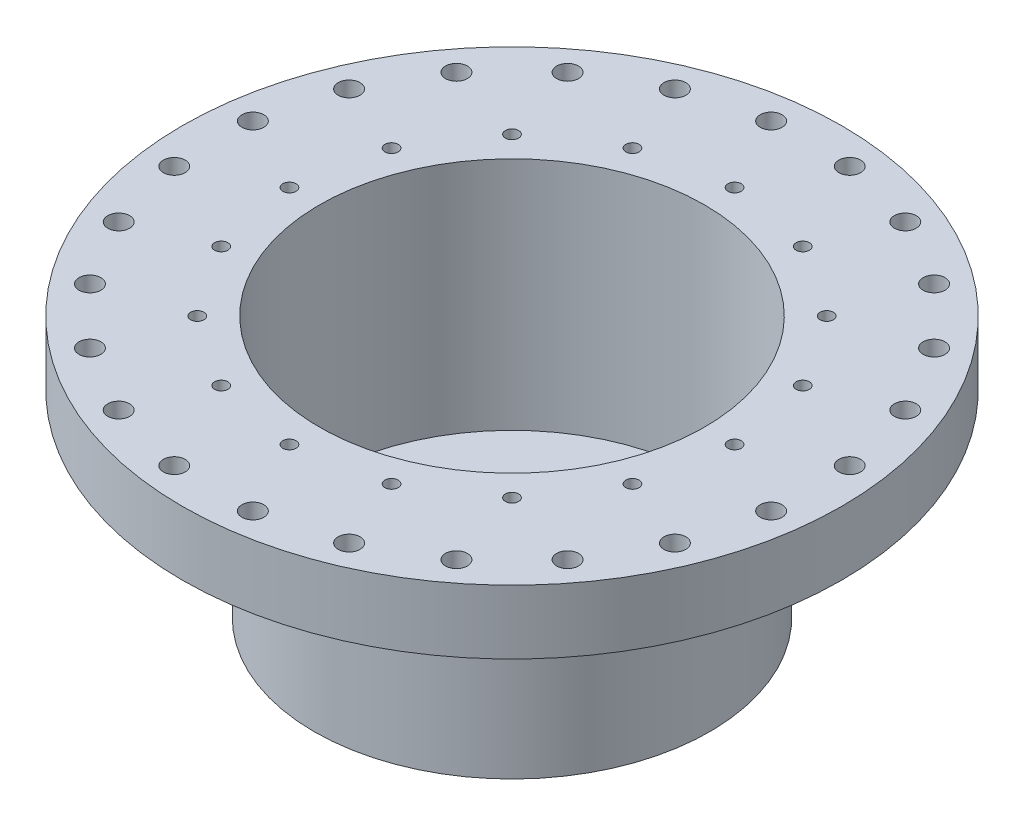
SolidWorks part; units mm, degrees
ref_plane "Front Plane" through (0, 0, 0) normal (0, 0, 1) x (1, 0, 0)
ref_plane "Top Plane" through (0, 0, 0) normal (0, 1, 0) x (1, 0, 0)
ref_plane "Right Plane" through (0, 0, 0) normal (1, 0, 0) x (0, 0, -1)
sketch "Sketch1" plane through (0, 0, 0) normal (0, 1, 0) x (1, 0, 0)
  circle A0 centre (0, 0) radius 76.2
  dimension "D1" = 152.4
extrude "Extrude1" add sketch "Sketch1" against normal blind 75.946
sketch "Sketch2" plane through (0, 0, 0) normal (0, 1, 0) x (1, 0, 0)
  circle A0 centre (0, 0) radius 127
extrude "Extrude2" add sketch "Sketch2" along normal blind 24.638
sketch "Sketch3" plane through (0, 0, 0) normal (0, 1, 0) x (1, 0, 0)
  circle A0 centre (0, 0) radius 74.168
  dimension "D1" = 148.336
extrude "Cut-Extrude1" cut sketch "Sketch3" against normal blind 65.9384 and the other way through all
sketch "Sketch4" plane through (0, 0, 0) normal (0, 1, 0) x (1, 0, 0)
  circle A0 centre (0, 0) radius 50.8
extrude "Cut-Extrude2" cut sketch "Sketch4" against normal through all
sketch "Sketch5" plane through (0, 0, 0) normal (0, 1, 0) x (1, 0, 0)
  line L0 (0, 0) -> (0, 108.8403)
  circle A0 centre (-15.1346, 114.959) radius 4.2164
  dimension "D2" = 115.951
ref_axis "Axis1" through (0, 130.3933, 0) along (0, -1, 0)
sketch "Sketch8" plane through (0, 24.638, 0) normal (0, 1, 0) x (1, 0, 0)
  point P0 (0, 85.725)
hole_wizard "1/4-20 Tapped Hole1" positions "3DSketch1" profile "Sketch11" tap size "1/4-20" standard "Ansi Inch"
sketch3d "3DSketch1"
  point P0 (0, 24.638, -85.725)
sketch "Sketch11" plane through (0, 24.638, -85.725) normal (1, 0, 0) x (0, 0, 1)
  line L0 (0, 0) -> (0, 18.0438)
  line L1 (0, 18.0438) -> (2.5527, 16.51)
  line L2 (2.5527, 16.51) -> (2.5527, 0)
  line L5 (2.5527, 0) -> (0, 0)
  line L10 (0, 18.0438) -> (-2.5527, 16.51) construction
  line L11 (0, -6.35) -> (0, 107.95) construction
  dimension "Tap Drill Dia." = 5.1054
  dimension "Tap Drill Depth" = 16.51
  dimension "Drill Angle" = 118
cosmetic thread "Hole Thread1" parameters "D1"=12.7, "D2"=6.35
pattern_circular "CirPattern2" count 16 over 360 about axis through (0, 130.3933, 0) along (0, -1, 0) of "1/4-20 Tapped Hole1"
ref_plane "Plane1" through (0, -75.946, 0) normal (0, -1, 0) x (1, 0, 0)
sketch "Sketch12" plane through (0, -75.946, 0) normal (0, -1, 0) x (1, 0, 0)
  point P0 (0, 0)
sketch "Sketch13" plane through (0, 0, 0) normal (1, 0, 0) x (0, 0, -1)
  line L0 (0, 0) -> (0, -106.8397)
ref_plane "Plane2" through (0, 24.638, 0) normal (0, 1, 0) x (-1, 0, 0)
sketch "Sketch14" plane through (0, 24.638, 0) normal (0, 1, 0) x (-1, 0, 0)
  line L0 (32.8055, 79.1996) -> (-48.6008, -117.3327)
  line L1 (-48.6008, -117.3327) -> (48.6008, 117.3327)
  circle A0 centre (0, 0) radius 127 construction
extrude "Cut-Extrude5" cut sketch "Sketch5" along normal through all contours A0
pattern_circular "CirPattern3" count 24 over 360 about axis through (0, 130.3933, 0) along (0, -1, 0) of "Cut-Extrude5"
sketch "Sketch16" plane through (0, 24.638, 0) normal (0, 1, 0) x (-1, 0, 0)
  circle A0 centre (90.17, 0) radius 9.525
  dimension "D1" = 19.05
  dimension "D2" = 90.17
extrude "Extrude3" [suppressed] add sketch "Sketch16" along normal blind 8.636
ref_plane "Plane3" [suppressed] through (0, 33.274, 0) normal (0, 1, 0) x (-1, 0, 0)
sketch "Sketch17" [suppressed] plane through (0, 33.274, 0) normal (0, 1, 0) x (-1, 0, 0)
  circle A0 centre (90.17, 0) radius 16.891
  dimension "D1" = 33.782
extrude "Extrude5" [suppressed] add sketch "Sketch17" along normal blind 7.239
sketch "Sketch21" [suppressed] plane through (0, 33.274, 0) normal (0, 1, 0) x (-1, 0, 0)
  circle A0 centre (90.17, 0) radius 7.874
  dimension "D1" = 15.748
  dimension "D2" = 90.17
extrude "Cut-Extrude6" [suppressed] cut sketch "Sketch21" along normal through all and the other way through all
ref_plane "Plane4" [suppressed] through (0, 40.513, 0) normal (0, 1, 0) x (-1, 0, 0)
sketch "Sketch22" [suppressed] plane through (0, 40.513, 0) normal (0, 1, 0) x (-1, 0, 0)
  circle A0 centre (87.376, 13.4874) radius 2.1844
  dimension "D1" = 4.3688
extrude "Cut-Extrude7" [suppressed] cut sketch "Sketch22" against normal blind 7.239
ref_axis "Axis2" [suppressed] through (-90.17, 40.513, 0) along (0, -1, 0)
pattern_circular "CirPattern4" [suppressed] count 6 over 360 about axis through (-90.17, 40.513, 0) along (0, -1, 0) of bodies 116
sketch "Sketch23" [suppressed] plane through (0, 40.513, 0) normal (0, 1, 0) x (-1, 0, 0)
  point P0 (90.17, 0)
sketch "Sketch24" [suppressed] plane through (0, 33.274, 0) normal (0, 1, 0) x (-1, 0, 0)
  point P0 (0, 0)
